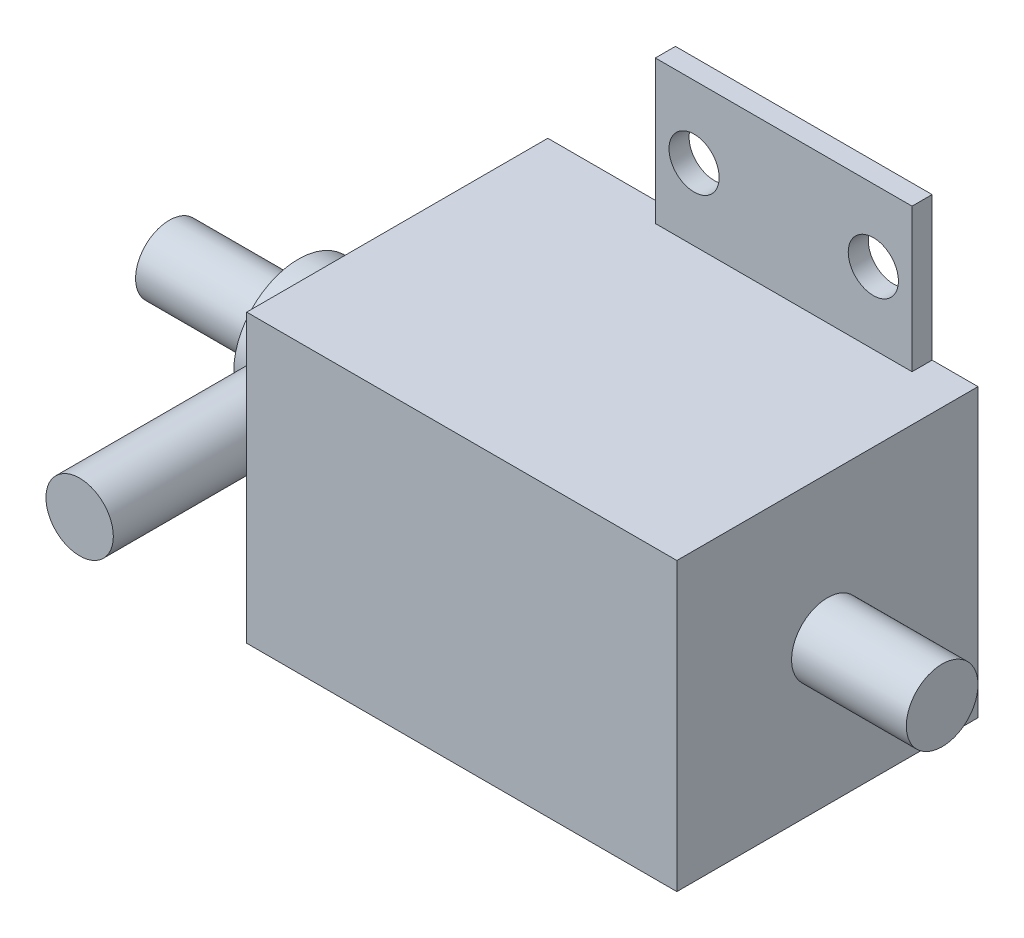
SolidWorks part; units mm, degrees
note: The reader was unsure of these and kept them because the rebuilt part matched: shared geometry of "Sketch8<2>".
ref_plane "Front Plane" through (0, 0, 0) normal (0, 0, 1) x (1, 0, 0)
ref_plane "Top Plane" through (0, 0, 0) normal (0, 1, 0) x (1, 0, 0)
ref_plane "Right Plane" through (0, 0, 0) normal (1, 0, 0) x (0, 0, -1)
sketch "Sketch1" plane through (0, 0, 0) normal (0, 0, 1) x (1, 0, 0)
  line L1 (0, 0) -> (30, 0)
  line L2 (0, 0) -> (0, 20)
  line L3 (0, 20) -> (30, 20)
  line L4 (30, 0) -> (30, 20)
  dimension "D1" = 20
  dimension "D2" = 30
extrude "Boss-Extrude1" add sketch "Sketch1" along normal blind 21
sketch "Sketch2" plane through (0, 20, 0) normal (0, 1, 0) x (1, 0, 0)
  line L0 (26.8, 0) -> (8.9, 0)
  line L1 (30, 0) -> (0, 0) construction
  line L2 (8.9, 0) -> (8.9, -1.4)
  line L3 (8.9, -1.4) -> (26.8, -1.4)
  line L4 (26.8, -1.4) -> (26.8, 0)
  dimension "D1" = 3.2
  dimension "D2" = 17.9
  dimension "D3" = 1.4
extrude "Boss-Extrude2" add sketch "Sketch2" along normal blind 10
sketch "Sketch3" plane through (30, 0, 0) normal (1, 0, 0) x (0, 0, -1)
  line L1 (-10.5, 20) -> (-10.5, 0) construction
  line L2 (-21, 20) -> (0, 20) construction
  line L3 (-21, 0) -> (0, 0) construction
  line L4 (-21, 10) -> (0, 10) construction
  line L5 (-21, 0) -> (-21, 20) construction
  line L6 (0, 0) -> (0, 20) construction
  circle A0 centre (-10.5, 10) radius 2.5
  point P15 (-10.5, 10)
  dimension "D1" = 5
extrude "Boss-Extrude3" add sketch "Sketch3" along normal blind 8
sketch "Sketch4" plane through (0, 0, 0) normal (-1, 0, 0) x (0, 0, 1)
  circle A0 centre (10.5, 10) radius 4.5
  dimension "D1" = 9
extrude "Boss-Extrude4" add sketch "Sketch4" along normal blind 6.9
sketch "Sketch5" plane through (-6.9, 0, 0) normal (-1, 0, 0) x (0, 0, 1)
  line L0 (21, 10) -> (0, 10) construction
  circle A0 centre (10.5, 10) radius 2.35
  dimension "D1" = 4.7
extrude "Boss-Extrude5" add sketch "Sketch5" along normal blind 9
sketch "Sketch6" plane through (-6.9, 0, 0) normal (-1, 0, 0) x (0, 0, 1)
  circle A2 centre (10.5, 10) radius 4.5 construction
  circle A3 centre (10.5, 10) radius 4.5 construction
  point P0 (15, 10)
  point P12 (10.5, 10)
ref_plane "Plane1" through (-6.9, 10, 15) normal (0, 0, 1) x (1, 0, 0)
sketch "Sketch7" plane through (-6.9, 10, 15) normal (0, 0, 1) x (1, 0, 0)
  line L0 (0, 0) -> (6.9, 0) construction
  line L1 (6.9, 10) -> (6.9, -10) construction
  line L2 (3.45, -4.5) -> (3.45, 4.5) construction
  line L3 (0, -4.5) -> (6.9, -4.5) construction
  line L4 (6.9, 4.5) -> (0, 4.5) construction
  circle A0 centre (3.45, 0) radius 2.35
  dimension "D1" = 4.7
extrude "Boss-Extrude6" add sketch "Sketch7" along normal blind 14.2 and the other way up to surface other way up to face at (-6.9, 10, 15)
sketch "Sketch8" plane through (0, 0, 1.4) normal (0, 0, 1) x (1, 0, 0)
  line L0 (8.9, 30) -> (8.9, 20) construction
  line L1 (17.85, 30) -> (17.85, 20) construction
  line L2 (8.9, 30) -> (26.8, 30) construction
  line L3 (8.9, 20) -> (26.8, 20) construction
  line L4 (8.9, 25) -> (26.8, 25) construction
  line L5 (26.8, 30) -> (26.8, 20) construction
  circle A0 centre (11.6, 25) radius 1.75
  circle A1 centre (24.1, 25) radius 1.75
  point P2 (9.85, 25)
  dimension "D2" = 3.5
  dimension "D1" = 12.5
extrude "Cut-Extrude1" cut sketch "Sketch8<2>" against normal through all
sketch "Sketch8<2>" plane through (0, 0, 1.4) normal (0, 0, 1) x (1, 0, 0) same geometry as "Sketch8"
sketch "Sketch9" plane through (0, 0, 1.4) normal (0, 0, 1) x (1, 0, 0)
  line L0 (-6.9, 14.5) -> (0, 14.5)
  line L1 (-6.9, 14.5) -> (0, 14.5)
  line L2 (0, 14.5) -> (0, 20)
  line L3 (0, 14.5) -> (0, 20)
  line L4 (0, 20) -> (8.9, 20)
  line L5 (0, 20) -> (8.9, 20)
  line L6 (8.9, 20) -> (8.9, 30)
  line L7 (8.9, 20) -> (8.9, 30)
  line L8 (8.9, 30) -> (26.8, 30)
  line L9 (8.9, 30) -> (26.8, 30)
  line L10 (26.8, 30) -> (26.8, 20)
  line L11 (26.8, 30) -> (26.8, 20)
  line L12 (26.8, 20) -> (30, 20)
  line L13 (26.8, 20) -> (30, 20)
  line L14 (30, 20) -> (30, 12.5)
  line L15 (30, 20) -> (30, 12.5)
  line L16 (30, 12.5) -> (38, 12.5)
  line L17 (30, 12.5) -> (38, 12.5)
  line L18 (38, 12.5) -> (38, 7.5)
  line L19 (38, 12.5) -> (38, 7.5)
  line L20 (38, 7.5) -> (30, 7.5)
  line L21 (38, 7.5) -> (30, 7.5)
  line L22 (30, 7.5) -> (30, 0)
  line L23 (30, 7.5) -> (30, 0)
  line L24 (30, 0) -> (0, 0)
  line L25 (30, 0) -> (0, 0)
  line L26 (0, 0) -> (0, 5.5)
  line L27 (0, 0) -> (0, 5.5)
  line L28 (0, 5.5) -> (-6.9, 5.5)
  line L29 (0, 5.5) -> (-6.9, 5.5)
  line L30 (-6.9, 5.5) -> (-6.9, 7.65)
  line L31 (-6.9, 5.5) -> (-6.9, 7.65)
  line L32 (-6.9, 7.65) -> (-15.9, 7.65)
  line L33 (-6.9, 7.65) -> (-15.9, 7.65)
  line L34 (-15.9, 7.65) -> (-15.9, 12.35)
  line L35 (-15.9, 7.65) -> (-15.9, 12.35)
  line L36 (-15.9, 12.35) -> (-6.9, 12.35)
  line L37 (-15.9, 12.35) -> (-6.9, 12.35)
  line L38 (-6.9, 12.35) -> (-6.9, 14.5)
  line L39 (-6.9, 12.35) -> (-6.9, 14.5)
  circle A0 centre (11.6, 25) radius 1.75
  circle A1 centre (11.6, 25) radius 1.75 construction
  circle A2 centre (24.1, 25) radius 1.75
  circle A3 centre (24.1, 25) radius 1.75 construction
extrude "Boss-Extrude7" add sketch "Sketch8" against normal through all
